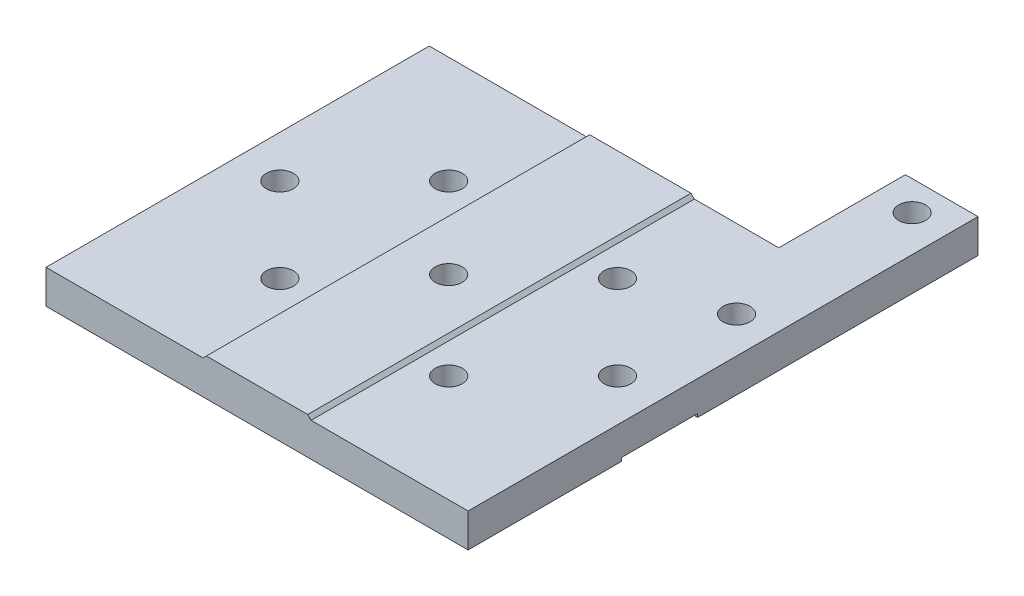
SolidWorks part; units mm, degrees
ref_plane "前视基准面" through (0, 0, 0) normal (0, 0, 1) x (1, 0, 0)
ref_plane "上视基准面" through (0, 0, 0) normal (0, 1, 0) x (1, 0, 0)
ref_plane "右视基准面" through (0, 0, 0) normal (1, 0, 0) x (0, 0, -1)
other "Configuration Table"
sketch "草图1" plane through (0, 0, 0) normal (0, 1, 0) x (1, 0, 0)
  line L1 (0, 0) -> (50, 0)
  line L2 (0, 0) -> (0, 45.4)
  line L3 (0, 45.4) -> (50, 45.4)
  line L4 (50, 0) -> (50, 45.4)
  circle A0 centre (15, 32.7) radius 1.6
  circle A1 centre (35, 32.7) radius 1.6
  circle A2 centre (35, 12.7) radius 1.6
  circle A3 centre (15, 12.7) radius 1.6
  dimension "D3" = 3.2
  dimension "D1" = 50
  dimension "D2" = 45.4
  dimension "D6" = 12.7
  dimension "D7" = 15
  dimension "D4" = 2
  dimension "D5" = 2
extrude "凸台-拉伸1" add sketch "草图1" along normal blind 4
sketch "草图2" plane through (0, 0, 0) normal (0, 0, 1) x (1, 0, 0)
  line L0 (0, 4) -> (50, 4) construction
  line L1 (19, 4) -> (31, 4)
  line L2 (19, 4) -> (19, 4.4)
  line L3 (19, 4.4) -> (31, 4.4)
  line L4 (31, 4) -> (31, 4.4)
  line L5 (0, 0) -> (50, 0) construction
  point P6 (25, 4.4)
  point P9 (25, 0)
  dimension "D1" = 0.4
  dimension "D2" = 12
  dimension "D3" = 0
extrude "凸台-拉伸2" add sketch "草图2" against normal up to surface (45.4 mm away) up to face at (25, 2, -45.4)
chamfer "倒角1" distance 0.4 angle 45 2 edges at (31, 4, -22.7) (19, 4, -22.7)
sketch "草图3" plane through (0, 0, 0) normal (0, -1, 0) x (-1, 0, 0)
  line L0 (0, 45.4) -> (0, 0) construction
  line L1 (0, 18.2) -> (-50, 18.2)
  line L2 (0, 18.2) -> (0, 27.2)
  line L3 (0, 27.2) -> (-50, 27.2)
  line L4 (-50, 18.2) -> (-50, 27.2)
  line L5 (-50, 0) -> (-50, 45.4) construction
  line L6 (0, 0) -> (-50, 0) construction
  point P8 (0, 22.7)
  dimension "D1" = 9
  dimension "D2" = 22.7
extrude "切除-拉伸1" cut sketch "草图3" against normal blind 0.4
sketch "草图4" plane through (0, 0.4, 0) normal (0, -1, 0) x (-1, 0, 0)
  line L0 (0, 18.2) -> (0, 27.2) construction
  circle A0 centre (-5, 22.7) radius 1.6
  circle A1 centre (-25, 22.7) radius 1.6
  circle A2 centre (-45, 22.7) radius 1.6
  point P4 (0, 22.7)
  dimension "D1" = 3.2
  dimension "D4" = 5
extrude "切除-拉伸2" cut sketch "草图4" against normal through all
sketch "草图5" plane through (0, 4, 0) normal (0, 1, 0) x (1, 0, 0)
  line L0 (50, 45.4) -> (31.4, 45.4) construction
  line L1 (50, 45.4) -> (41.4, 45.4)
  line L2 (50, 45.4) -> (50, 60.4)
  line L3 (50, 60.4) -> (41.4, 60.4)
  line L4 (41.4, 45.4) -> (41.4, 60.4)
  line L5 (50, 0) -> (50, 45.4) construction
  dimension "D1" = 8.6
  dimension "D2" = 0
  dimension "D3" = 15
extrude "凸台-拉伸3" add sketch "草图5" against normal blind 4
sketch "草图6" plane through (0, 0, 0) normal (0, -1, 0) x (1, 0, 0)
  line L0 (50, -60.4) -> (41.4, -60.4) construction
  line L1 (50, -27.2) -> (50, -60.4) construction
  circle A0 centre (45.7, -56.9) radius 1.6
  circle A1 centre (45.7, -36.1) radius 1.6
  point P4 (45.7, -60.4)
  dimension "D1" = 3.2
  dimension "D2" = 3.5
  dimension "D3" = 4.3
  dimension "D4" = 0
  dimension "D5" = 20.8
  dimension "D6" = 3.2
extrude "切除-拉伸3" cut sketch "草图6" against normal blind 4
equation "\"D7@草图1\"=\"D1@草图1\"/2-10"
equation "\"D6@草图1\"=\"D2@草图1\"/2-10"
equation "\"D2@草图3\"=\"D2@草图1\"/2"
equation "\"D4@草图4\"=\"D1@草图1\"/2-20"
